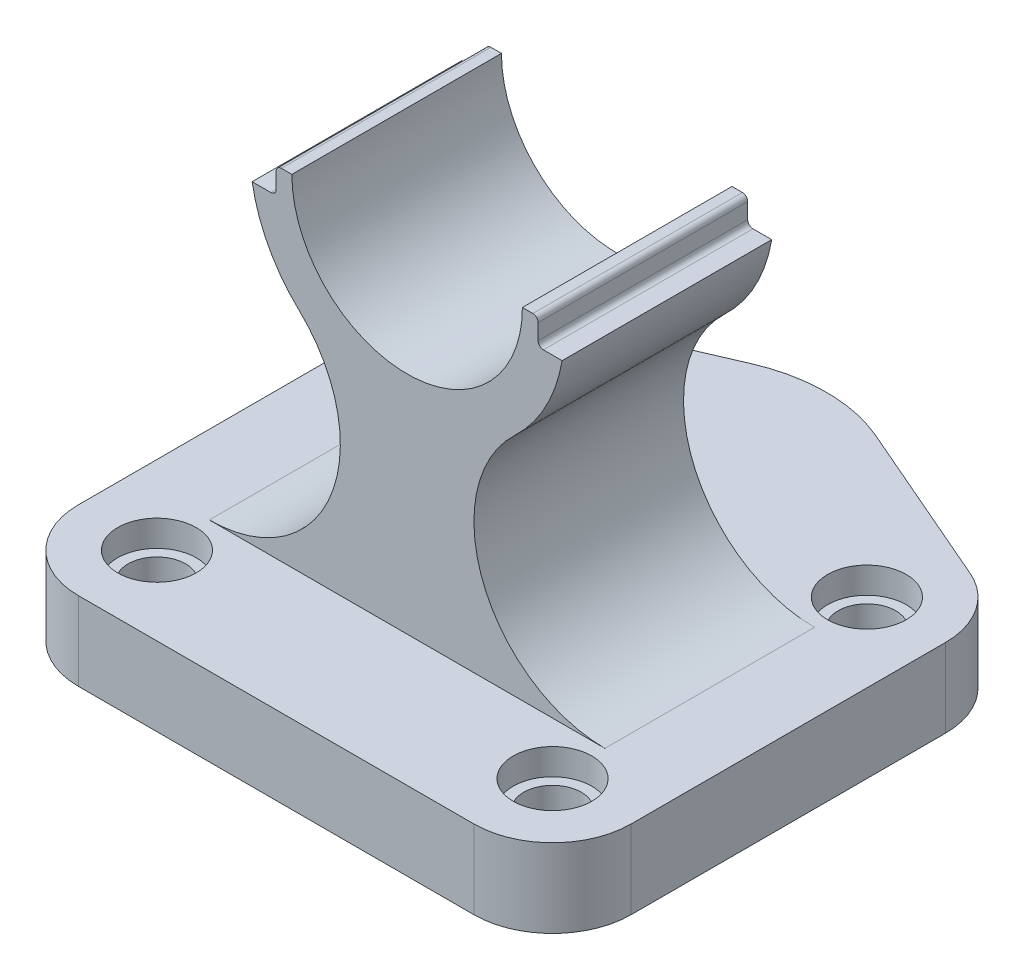
SolidWorks part; units mm, degrees
ref_plane "Front Plane" through (0, 0, 0) normal (0, 0, 1) x (1, 0, 0)
ref_plane "Top Plane" through (0, 0, 0) normal (0, 1, 0) x (1, 0, 0)
ref_plane "Right Plane" through (0, 0, 0) normal (1, 0, 0) x (0, 0, -1)
sketch "Sketch1" plane through (0, 0, 0) normal (0, 1, 0) x (1, 0, 0)
  line L24 (52.75, -30) -> (52.75, 30)
  line L25 (-37.75, -45) -> (37.75, -45)
  line L26 (-52.75, -30) -> (-52.75, 30)
  line L31 (-43.7103, 43.765) -> (-11.9205, 57.53)
  line L32 (43.7103, 43.765) -> (11.9205, 57.53)
  line L33 (31.8783, 25.3338) -> (37.75, 30) construction
  circle A12 centre (-37.75, 30) radius 7.5
  circle A14 centre (-37.75, 30) radius 5.5
  arc A15 (52.75, -30) -> (37.75, -45) centre (37.75, -30) cw
  arc A16 (-37.75, -45) -> (-52.75, -30) centre (-37.75, -30) cw
  circle A17 centre (37.75, 30) radius 5.5
  circle A18 centre (37.75, 30) radius 7.5
  circle A19 centre (37.75, -30) radius 7.5
  circle A20 centre (37.75, -30) radius 5.5
  circle A21 centre (-37.75, -30) radius 5.5
  circle A22 centre (-37.75, -30) radius 7.5
  arc A23 (11.9205, 57.53) -> (-11.9205, 57.53) centre (0, 30) ccw
  arc A24 (43.7103, 43.765) -> (52.75, 30) centre (37.75, 30) cw
  arc A25 (-43.7103, 43.765) -> (-52.75, 30) centre (-37.75, 30) ccw
  point P0 (0, 0)
  point P8 (0, 0)
  dimension "D3" = 15
  dimension "D4" = 2
  dimension "D7" = 15
  dimension "D6" = 15
  dimension "D8" = 30
  dimension "D1" = 60
  dimension "D2" = 75.5
extrude "Boss-Extrude1" add sketch "Sketch1" along normal blind 15 contours L26 A25 L31 A23 L32 A24 L24 A15 L25 A16
extrude "Cut-Extrude2" cut sketch "Sketch1<5>" along normal blind 15 contours A22 | A12 | A18 | A19
sketch "Sketch1<5>" plane through (0, 0, 0) normal (0, 1, 0) x (1, 0, 0) same geometry as "Sketch1"
extrude "Boss-Extrude2" add sketch "Sketch1<6>" along normal blind 10 contours A18 A17 | A12 A14 | A22 A21 | A19 A20 region at (-45.0379, 0, -30) region at (30.4621, 0, -30) region at (30.4621, 0, 30) region at (-45.0379, 0, 30)
sketch "Sketch1<6>" plane through (0, 0, 0) normal (0, 1, 0) x (1, 0, 0) same geometry as "Sketch1"
sketch "Sketch2" plane through (0, 0, 0) normal (0, 0, 1) x (1, 0, 0)
  line L0 (-25, 79) -> (-25, 76)
  line L2 (-37.75, 15) -> (37.75, 15) construction
  line L3 (-37.7492, 15) -> (37.7492, 15)
  line L4 (-24, 80) -> (-22, 80)
  line L6 (-29.5804, 75) -> (-26, 75)
  line L7 (29.5804, 75) -> (26, 75)
  line L8 (24, 80) -> (22, 80)
  line L9 (25, 79) -> (25, 76)
  arc A0 (-22, 80) -> (22, 80) centre (0, 80) ccw
  arc A1 (-29.5804, 75) -> (-20.5905, 58.1818) centre (0, 80) ccw
  arc A2 (-26, 75) -> (-25, 76) centre (-26, 76) ccw
  arc A3 (-25, 79) -> (-24, 80) centre (-24, 79) cw
  arc A4 (25, 79) -> (24, 80) centre (24, 79) ccw
  arc A5 (26, 75) -> (25, 76) centre (26, 76) cw
  arc A6 (20.5905, 58.1818) -> (37.7492, 15) centre (37.7492, 40) ccw
  arc A7 (-20.5905, 58.1818) -> (-37.7492, 15) centre (-37.7492, 40) cw
  arc A8 (20.5905, 58.1818) -> (29.5804, 75) centre (0, 80) ccw
  point P9 (-25, 75)
  point P18 (-25, 80)
  point P27 (25, 75)
  dimension "D2" = 44
  dimension "D3" = 60
  dimension "D4" = 1
  dimension "D7" = 50
  dimension "D1" = 80
  dimension "D6" = 5
  dimension "D5" = 50
extrude "Boss-Extrude3" add sketch "Sketch2" along normal mid plane 40 contours A0 L8 A4 L9 A5 L7 A8 A6 L3 A7 A1 L6 A2 L0 A3 L4
